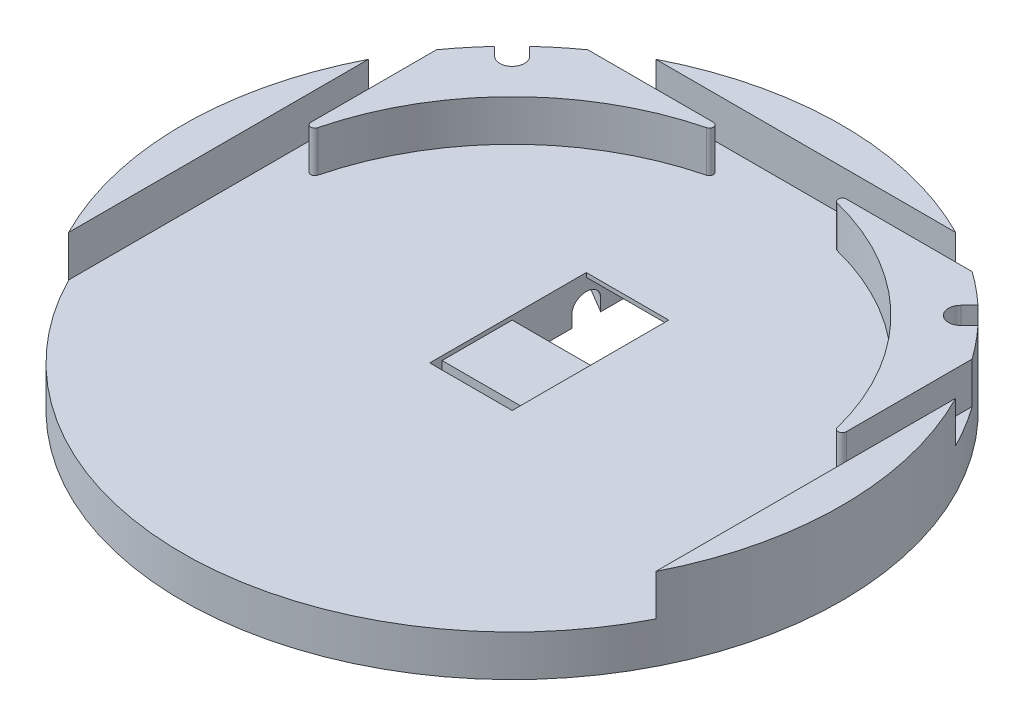
SolidWorks part; units mm, degrees
material "6061 Alloy"
ref_plane "Front Plane" through (0, 0, 0) normal (0, 0, 1) x (1, 0, 0)
ref_plane "Top Plane" through (0, 0, 0) normal (0, 1, 0) x (1, 0, 0)
ref_plane "Right Plane" through (0, 0, 0) normal (1, 0, 0) x (0, 0, -1)
sketch "Sketch1" plane through (0, 0, 0) normal (0, 1, 0) x (1, 0, 0)
  line L0 (16.51, 11.8458) -> (16.51, -11.8458)
  line L1 (-16.51, 11.8458) -> (-16.51, -11.8458)
  line L2 (18.0975, 9.2403) -> (18.0975, -9.2403)
  line L3 (-18.0975, 9.2403) -> (-18.0975, -9.2403)
  line L4 (-11.8458, 16.51) -> (11.8458, 16.51)
  line L5 (-9.2403, 18.0975) -> (9.2403, 18.0975)
  line L6 (-13.8296, 13.8296) -> (-11.8458, 16.51) construction
  line L7 (-13.8296, 13.8296) -> (-16.51, 11.8458) construction
  line L8 (-13.2908, 14.3684) -> (-13.8195, 14.8971)
  line L9 (-14.3684, 13.2908) -> (-14.8971, 13.8195)
  line L10 (0, 0) -> (-13.8296, 13.8296) construction
  line L11 (0, 0) -> (13.8296, 13.8296) construction
  line L12 (13.2908, 14.3684) -> (13.8195, 14.8971)
  line L13 (14.3684, 13.2908) -> (14.8971, 13.8195)
  circle A0 centre (0, 0) radius 20.32
  circle A1 centre (0, 0) radius 16.51
  circle A2 centre (13.8296, 13.8296) radius 0.762
  circle A3 centre (-13.8296, 13.8296) radius 0.762
  point P23 (-16.51, 0)
  point P24 (16.51, 0)
  point P25 (0, 16.51)
  dimension "D1" = 40.64
  dimension "D2" = 33.02
  dimension "D5" = 1.524
  dimension "D3" = 1.5875
sketch "Sketch2" plane through (0, 0, 0) normal (0, 1, 0) x (1, 0, 0)
  line L0 (-14.3684, 13.2908) -> (-14.8971, 13.8195) construction
  line L1 (-13.8195, 14.8971) -> (-13.2908, 14.3684)
  line L2 (-14.8971, 13.8195) -> (-14.3684, 13.2908)
  line L3 (13.8195, 14.8971) -> (13.2908, 14.3684)
  line L4 (14.8971, 13.8195) -> (14.3684, 13.2908)
  arc A0 (-13.8195, 14.8971) -> (13.8195, 14.8971) centre (0, 0) cw
  arc A1 (-13.2908, 14.3684) -> (-14.3684, 13.2908) centre (-13.8296, 13.8296) cw
  arc A2 (14.3684, 13.2908) -> (13.2908, 14.3684) centre (13.8296, 13.8296) cw
  arc A3 (14.8971, 13.8195) -> (-14.8971, 13.8195) centre (0, 0) cw
extrude "Boss-Extrude2" add sketch "Sketch2" along normal blind 5.08
sketch "Sketch3" plane through (0, 5.08, 0) normal (0, 1, 0) x (1, 0, 0)
  line L0 (-18.0975, 9.2403) -> (-18.0975, -9.2403)
  line L1 (-16.51, 11.8458) -> (-16.51, 4.0956)
  line L2 (-4.0956, 16.51) -> (-11.8458, 16.51)
  line L3 (-9.2403, 18.0975) -> (9.2403, 18.0975) construction
  line L4 (16.51, 11.8458) -> (16.51, 4.0956)
  line L5 (18.0975, -9.2403) -> (18.0975, 9.2403)
  line L6 (-9.2403, 18.0975) -> (9.2403, 18.0975)
  line L7 (-11.8458, 16.51) -> (11.8458, 16.51) construction
  line L8 (11.8458, 16.51) -> (4.0956, 16.51)
  arc A0 (-16.0097, 4.0336) -> (-4.0336, 16.0097) centre (0, 0) cw
  arc A1 (-18.0975, 9.2403) -> (-16.51, 11.8458) centre (0, 0) cw
  arc A2 (-16.0097, 4.0336) -> (-16.51, 4.0956) centre (-16.256, 4.0956) cw
  arc A3 (-4.0956, 16.51) -> (-4.0336, 16.0097) centre (-4.0956, 16.256) cw
  arc A4 (16.51, 11.8458) -> (18.0975, 9.2403) centre (0, 0) cw
  arc A5 (18.0975, -9.2403) -> (-18.0975, -9.2403) centre (0, 0) cw
  arc A6 (-11.8458, 16.51) -> (-9.2403, 18.0975) centre (0, 0) cw
  arc A7 (9.2403, 18.0975) -> (11.8458, 16.51) centre (0, 0) cw
  arc A8 (4.0336, 16.0097) -> (16.0097, 4.0336) centre (0, 0) cw
  arc A9 (4.0956, 16.51) -> (4.0336, 16.0097) centre (4.0956, 16.256) ccw
  arc A10 (16.51, 4.0956) -> (16.0097, 4.0336) centre (16.256, 4.0956) cw
  point P17 (-16.51, 0)
  point P38 (0, 16.51)
  point P40 (16.51, 0)
  dimension "D1" = 0.254
  dimension "D2" = 0.254
  dimension "D3" = 0.254
  dimension "D4" = 0.254
extrude "Cut-Extrude1" cut sketch "Sketch3" against normal blind 2.54
sketch "Sketch7" plane through (0, 2.54, 0) normal (0, 1, 0) x (1, 0, 0)
  line L0 (-2.54, -1.778) -> (2.54, -1.778)
  line L1 (2.54, 2.54) -> (-2.54, 2.54)
  line L2 (2.54, 2.54) -> (2.54, -2.54)
  line L3 (2.54, -2.54) -> (-2.54, -2.54)
  line L4 (-2.54, 2.54) -> (-2.54, -2.54)
  line L5 (2.54, 2.54) -> (-2.54, -2.54) construction
  line L6 (2.54, -2.54) -> (-2.54, 2.54) construction
  line L7 (2.54, 7.112) -> (-2.54, 7.112)
  line L8 (-2.54, -2.54) -> (2.54, -2.54)
  line L9 (-2.54, -2.54) -> (-2.54, -3.302)
  line L10 (-2.54, -3.302) -> (2.54, -3.302)
  line L11 (2.54, -2.54) -> (2.54, -3.302)
  line L12 (-2.54, 2.54) -> (2.54, 2.54)
  line L13 (-2.54, 2.54) -> (-2.54, 10.922)
  line L14 (-2.54, 10.922) -> (2.54, 10.922)
  line L15 (2.54, 2.54) -> (2.54, 10.922)
  point P0 (0, 0)
  dimension "D1" = 0.762
  dimension "D2" = 0.762
  dimension "D3" = 13.462
  dimension "D4" = 3.81
sketch "Sketch8" plane through (0, 2.54, 0) normal (0, 1, 0) x (1, 0, 0)
  line L1 (-2.54, 2.54) -> (2.54, 2.54)
  line L2 (-2.54, 2.54) -> (-2.54, -1.778)
  line L3 (-2.54, -1.778) -> (2.54, -1.778)
  line L4 (2.54, 2.54) -> (2.54, -1.778)
extrude "Cut-Extrude3" cut sketch "Sketch8" against normal blind 0.254
sketch "Sketch12" plane through (0, 0, 0) normal (0, -1, 0) x (1, 0, 0)
  line L1 (-2.54, 3.302) -> (2.54, 3.302)
  line L2 (-2.54, 3.302) -> (-2.54, 2.54)
  line L3 (-2.54, 2.54) -> (2.54, 2.54)
  line L4 (2.54, 3.302) -> (2.54, 2.54)
  line L5 (-2.54, -7.112) -> (2.54, -7.112)
  line L6 (-2.54, -7.112) -> (-2.54, -10.922)
  line L7 (-2.54, -10.922) -> (2.54, -10.922)
  line L8 (2.54, -7.112) -> (2.54, -10.922)
extrude "Cut-Extrude10" cut sketch "Sketch12" against normal blind 2.286
sketch "Sketch13" plane through (0, 2.54, 0) normal (0, 1, 0) x (1, 0, 0)
  line L1 (-2.54, 7.112) -> (2.54, 7.112)
  line L2 (-2.54, 7.112) -> (-2.54, 2.54)
  line L3 (-2.54, 2.54) -> (2.54, 2.54)
  line L4 (2.54, 7.112) -> (2.54, 2.54)
  line L5 (-2.54, -1.778) -> (2.54, -1.778)
  line L6 (-2.54, -1.778) -> (-2.54, -2.54)
  line L7 (-2.54, -2.54) -> (2.54, -2.54)
  line L8 (2.54, -1.778) -> (2.54, -2.54)
extrude "Cut-Extrude11" cut sketch "Sketch13" against normal through all
sketch "Sketch15" plane through (0, 0, 0) normal (0, -1, 0) x (1, 0, 0)
  line L0 (-14.2192, -13.1748) -> (-2.54, -6.2253)
  line L1 (-2.54, -2.54) -> (-2.54, -10.922) construction
  line L2 (-13.4399, -14.4844) -> (-1.0498, -7.112)
  line L3 (2.54, -7.112) -> (-2.54, -7.112) construction
  line L4 (-2.54, -7.112) -> (-2.1504, -7.7668) construction
  line L5 (-2.54, -7.112) -> (-2.9296, -6.4572) construction
  line L6 (-2.54, -6.2253) -> (-2.54, -7.112)
  line L7 (-2.54, -7.112) -> (-1.0498, -7.112)
  arc A0 (-14.2192, -13.1748) -> (-13.4399, -14.4844) centre (-13.8296, -13.8296) cw
  circle A1 centre (-13.8296, -13.8296) radius 0.762 construction
extrude "Cut-Extrude12" cut sketch "Sketch15" against normal blind 1.524
fillet "Fillet1" radius 0.762 2 edges at (-7.9491, 1.524, -11.2172) (-13.3244, 1.524, -14.4021)
fillet "Fillet3" radius 0.762 3 edges at (-2.54, 1.524, -6.6687) (-13.6421, 1.524, -13.091) (-8.3796, 1.524, -9.7)
